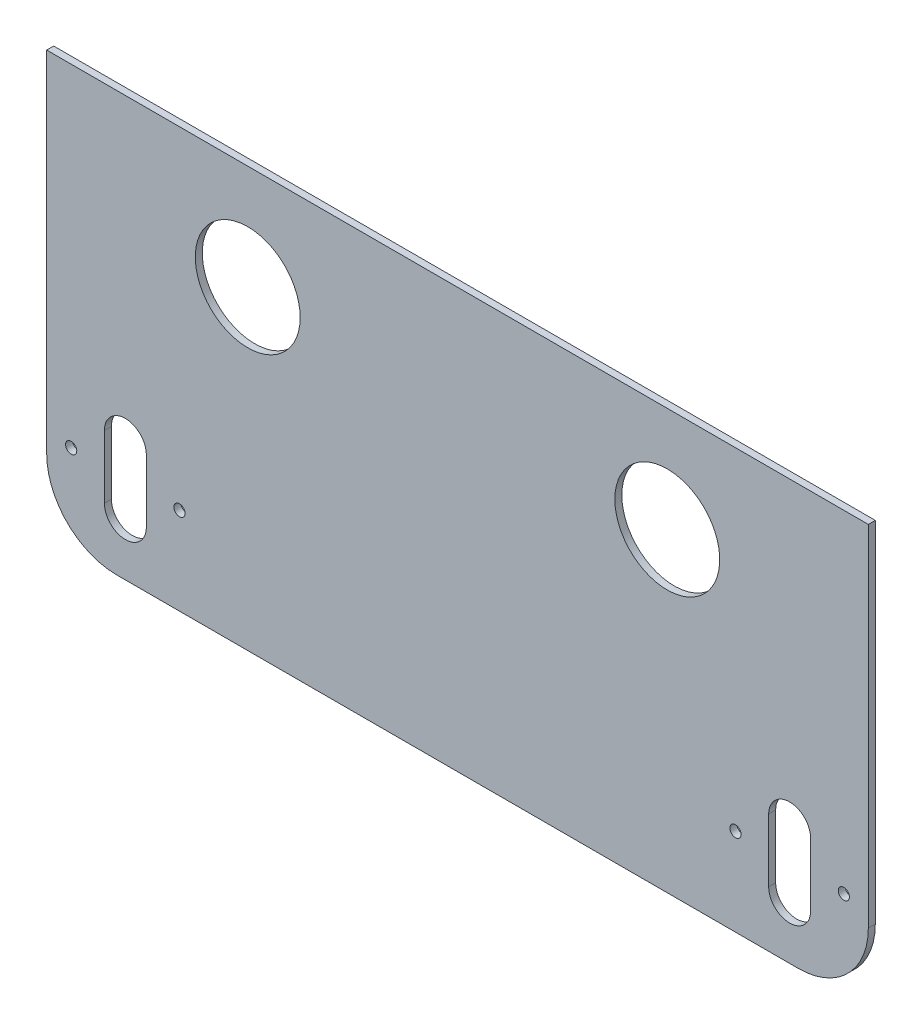
SolidWorks part; units mm, degrees
ref_plane "前视基准面" through (0, 0, 0) normal (0, 0, 1) x (1, 0, 0)
ref_plane "上视基准面" through (0, 0, 0) normal (0, 1, 0) x (1, 0, 0)
ref_plane "右视基准面" through (0, 0, 0) normal (1, 0, 0) x (0, 0, -1)
other "Configuration Table"
sketch "草图1" plane through (0, 0, 0) normal (0, 0, 1) x (1, 0, 0)
  line L0 (43.2911, 44.7063) -> (43.2911, -75.2937) construction
  line L1 (-74.2089, 44.7063) -> (160.7911, 44.7063)
  line L2 (-74.2089, 44.7063) -> (-74.2089, -75.2937)
  line L3 (-74.2089, -75.2937) -> (160.7911, -75.2937)
  line L4 (160.7911, 44.7063) -> (160.7911, -75.2937)
  line L5 (-74.2089, 14.7063) -> (160.7911, 14.7063) construction
  circle A0 centre (-16.7089, 14.7063) radius 15
  circle A1 centre (103.2911, 14.7063) radius 15
  dimension "D4" = 30
  dimension "D1" = 235
  dimension "D2" = 120
  dimension "D3" = 30
  dimension "D5" = 60
extrude "凸台-拉伸1" add sketch "草图1" along normal blind 2
fillet "圆角1" radius 20 1 edges at (160.7911, -75.2937, 1)
fillet "圆角2" radius 20 1 edges at (-74.2089, -75.2937, 1)
sketch "草图3" plane through (0, 0, 2) normal (0, 0, 1) x (1, 0, 0)
  line L0 (43.2911, 44.7063) -> (43.2911, -75.2937) construction
  line L1 (160.7911, 44.7063) -> (-74.2089, 44.7063) construction
  line L2 (-54.2089, -75.2937) -> (140.7911, -75.2937) construction
  line L3 (-74.2089, -50.2937) -> (160.7911, -50.2937) construction
  line L4 (-74.2089, 44.7063) -> (-74.2089, -55.2937) construction
  line L5 (160.7911, -55.2937) -> (160.7911, 44.7063) construction
  line L6 (-51.7089, -59.2937) -> (-51.7089, -41.2937) construction
  line L7 (-57.7089, -59.2937) -> (-57.7089, -41.2937)
  line L8 (-45.7089, -59.2937) -> (-45.7089, -41.2937)
  line L9 (138.2911, -59.2937) -> (138.2911, -41.2937) construction
  line L10 (144.2911, -59.2937) -> (144.2911, -41.2937)
  line L11 (132.2911, -59.2937) -> (132.2911, -41.2937)
  circle A0 centre (-51.7089, -50.2937) radius 15.5 construction
  circle A1 centre (-36.2089, -50.2937) radius 1.6
  circle A2 centre (-67.2089, -50.2937) radius 1.6
  circle A3 centre (153.7911, -50.2937) radius 1.6
  circle A4 centre (122.7911, -50.2937) radius 1.6
  arc A5 (-57.7089, -59.2937) -> (-45.7089, -59.2937) centre (-51.7089, -59.2937) ccw
  arc A6 (-45.7089, -41.2937) -> (-57.7089, -41.2937) centre (-51.7089, -41.2937) ccw
  arc A7 (144.2911, -59.2937) -> (132.2911, -59.2937) centre (138.2911, -59.2937) cw
  arc A8 (132.2911, -41.2937) -> (144.2911, -41.2937) centre (138.2911, -41.2937) cw
  point P23 (-51.7089, -50.2937)
  point P31 (138.2911, -50.2937)
  dimension "D2" = 31
  dimension "D3" = 3.2
  dimension "D5" = 6
  dimension "D1" = 25
  dimension "D4" = 95
  dimension "D6" = 18
extrude "切除-拉伸1" cut sketch "草图3" against normal blind 10
